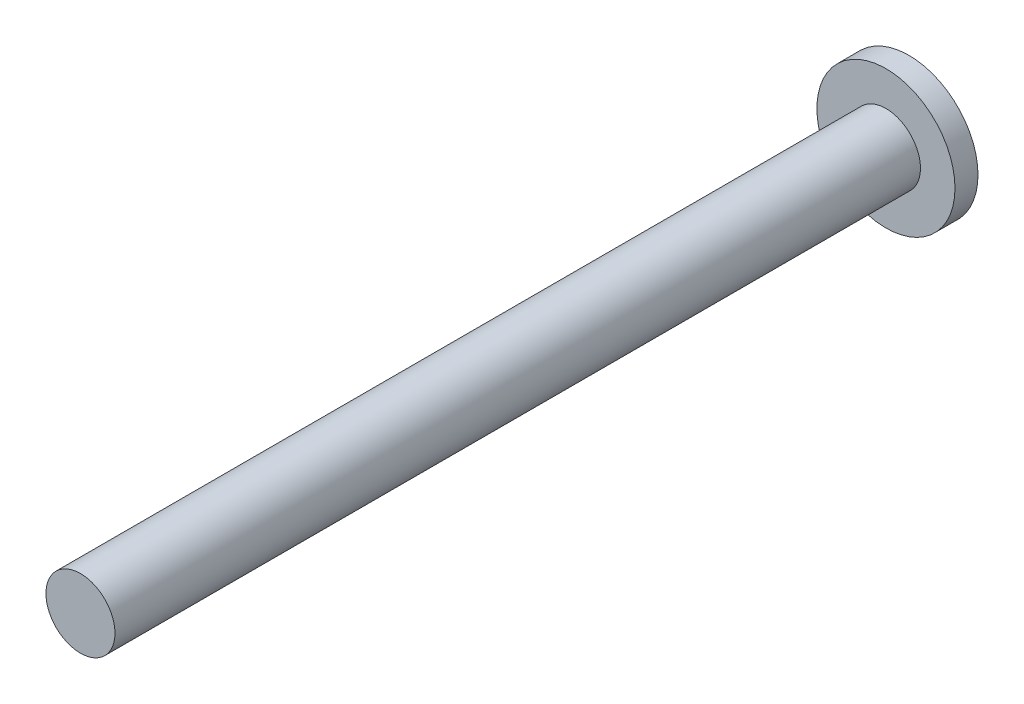
SolidWorks part; units mm, degrees
ref_plane "Plan de face" through (0, 0, 0) normal (0, 0, 1) x (1, 0, 0)
ref_plane "Plan de dessus" through (0, 0, 0) normal (0, 1, 0) x (1, 0, 0)
ref_plane "Plan de droite" through (0, 0, 0) normal (1, 0, 0) x (0, 0, -1)
sketch "Esquisse1" plane through (0, 0, 0) normal (0, 0, 1) x (1, 0, 0)
  circle A0 centre (0, 0) radius 3
  circle A1 centre (0, 0) radius 1.5
  dimension "D1" = 3
  dimension "D2" = 6
extrude "Boss.-Extru.1" add sketch "Esquisse1" along normal blind 35 contours A1 region at (0, 0, 0)
extrude "Boss.-Extru.2" add sketch "Esquisse1<3>" against normal blind 1 contours A0 A1 | A1 region at (-2.9151, 0, 0) region at (0, 0, 0)
sketch "Esquisse1<3>" plane through (0, 0, 0) normal (0, 0, 1) x (1, 0, 0) same geometry as "Esquisse1"
